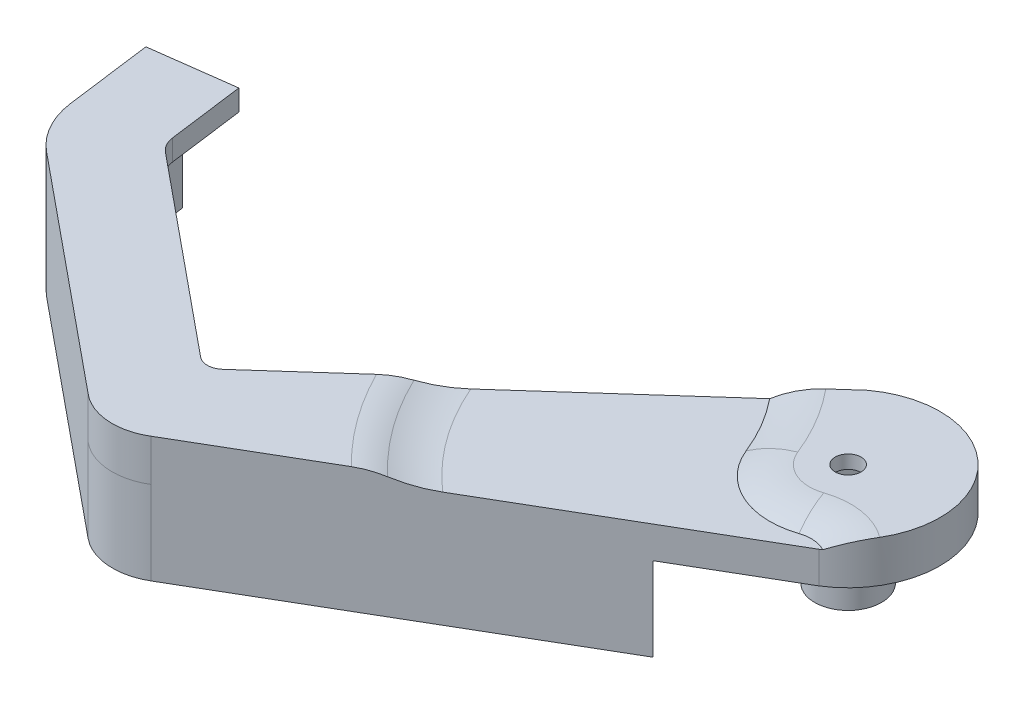
SolidWorks part; units mm, degrees
ref_plane "Front Plane" through (0, 0, 0) normal (0, 0, 1) x (1, 0, 0)
ref_plane "Top Plane" through (0, 0, 0) normal (0, 1, 0) x (1, 0, 0)
ref_plane "Right Plane" through (0, 0, 0) normal (1, 0, 0) x (0, 0, -1)
sketch "Sketch1" plane through (0, 0, 0) normal (0, 1, 0) x (1, 0, 0)
  circle A0 centre (0, 0) radius 10.3349
  dimension "D1" = 20.6698
extrude "Boss-Extrude1" add sketch "Sketch1" along normal blind 4
sketch "Sketch2" plane through (0, 0, 0) normal (0, -1, 0) x (1, 0, 0)
  circle A0 centre (0, 0) radius 4
other "Move Face1" flip direction yes face at (0, 0, 10.3349) offset 3 parameters "D1"=3
sketch "Sketch5" plane through (0, 3, 0) normal (0, -1, 0) x (1, 0, 0)
  line L0 (0, 0) -> (-48.7465, 34.9826) construction
  line L1 (-48.7465, 34.9826) -> (-78.7465, 10.3971) construction
  line L2 (0, 0) -> (-78.7465, 10.3971) construction
  line L3 (-78.7465, 10.3971) -> (-80.7177, -4.5326) construction
  line L5 (-75.4582, -2.5675) -> (-74.0969, 7.743)
  line L6 (-74.0969, 7.743) -> (-48.5447, 28.6834)
  line L12 (-6.5426, -8.8428) -> (-48.5447, 28.6834)
  line L13 (-52.8156, 38.1124) -> (-83.396, 13.0512)
  line L15 (-75.4582, -2.5675) -> (-85.2869, -1.2698)
  line L16 (-85.2869, -1.2698) -> (-83.396, 13.0512)
  line L17 (-44.6294, 38.7624) -> (5.2508, 9.6659)
  arc A1 (-52.8156, 38.1124) -> (-44.6294, 38.7624) centre (-48.2723, 32.7672) cw
  arc A3 (5.2508, 9.6659) -> (-6.5426, -8.8428) centre (0, 0) cw
  point P9 (-80.7177, -4.5326)
  point P15 (0, 0)
  dimension "D1" = 10.4
  dimension "D2" = 60
  dimension "D3" = 30
  dimension "D4" = 105
  dimension "D7" = 5
  dimension "D12" = 33.0367
extrude "Boss-Extrude3" add sketch "Sketch5" along normal blind 5
sketch "Sketch6" plane through (0, -2, 0) normal (0, -1, 0) x (1, 0, 0)
  circle A0 centre (0, 0) radius 6.3
  dimension "D1" = 12.6
extrude "Boss-Extrude4" add sketch "Sketch6" along normal blind 0.3
other "Move Face2" flip direction yes face at (0, 4, 10.3349) offset 1 parameters "D1"=1
sketch "Sketch8" plane through (0, -2, 0) normal (0, -1, 0) x (1, 0, 0)
  line L0 (-85.2869, -1.2698) -> (-81.4016, -1.7828)
  line L1 (-85.2869, -1.2698) -> (-75.4582, -2.5675) construction
  line L2 (-81.4016, -1.7828) -> (-79.6672, 11.3539)
  line L3 (-79.6672, 11.3539) -> (-48.9483, 36.5285)
  line L9 (-83.396, 13.0512) -> (-85.2869, -1.2698)
  line L10 (-12.814, 12.5754) -> (-48.9483, 36.5285)
  line L11 (-52.8156, 38.1124) -> (-83.396, 13.0512)
  line L12 (-44.6294, 38.7624) -> (-6.72, 16.6488)
  line L13 (-52.8156, 38.1124) -> (-83.396, 13.0512) construction
  arc A0 (-6.72, 16.6488) -> (-12.814, 12.5754) centre (0, 0) ccw
  arc A1 (-44.6294, 38.7624) -> (-52.8156, 38.1124) centre (-48.2574, 32.5794) ccw
  arc A2 (-44.6294, 38.7624) -> (-52.8156, 38.1124) centre (-48.2723, 32.7672) ccw construction
extrude "Boss-Extrude5" add sketch "Sketch8" along normal blind 10
sketch "Sketch9" plane through (0, -2, 0) normal (0, -1, 0) x (1, 0, 0)
  line L1 (-19.0217, 1.1217) -> (-75.4582, -2.5675)
  line L2 (-75.4582, -2.5675) -> (-81.4016, -1.7828)
  line L3 (-81.4016, -1.7828) -> (-79.6672, 11.3539)
  line L4 (-81.4016, -1.7828) -> (-79.6672, 11.3539) construction
  line L5 (-79.6672, 11.3539) -> (-48.9483, 36.5285)
  line L6 (-48.9483, 36.5285) -> (-13.7475, 13.1943)
  arc A0 (-13.7475, 13.1943) -> (-19.0217, 1.1217) centre (0, 0) ccw
  point P4 (0, 0)
  point P5 (0, 0)
  dimension "D1" = 1.12
extrude "Cut-Extrude3" cut sketch "Sketch9" against normal blind 2.5
ref_axis "Axis2" through (0, -2, 0) along (0, 1, 0)
ref_plane "Plane1" through (0, 0, 0) normal (-0.5525, 0, -0.8335) x (-0.8335, 0, 0.5525)
sketch "Sketch13" plane through (0, -2.3, 0) normal (0, -1, 0) x (1, 0, 0)
  circle A2 centre (0, 0) radius 4
  dimension "D1" = 8
extrude "Boss-Extrude6" add sketch "Sketch13" along normal blind 7
sketch "Sketch14" plane through (0, -9.3, 0) normal (0, -1, 0) x (1, 0, 0)
  circle A0 centre (0, 0) radius 1.55
  dimension "D1" = 3.1
extrude "Cut-Extrude6" cut sketch "Sketch14" against normal blind 14.3
ref_plane "Plane2" through (0, -1.1, 0) normal (0, -1, 0) x (-1, 0, 0)
sketch "Sketch15" plane through (0, -1.1, 0) normal (0, -1, 0) x (-1, 0, 0)
  line L1 (2.0704, -2.7773) -> (3.4404, 0.4043)
  line L2 (3.4404, 0.4043) -> (1.37, 3.1817)
  line L3 (1.37, 3.1817) -> (-2.0704, 2.7773)
  line L4 (-2.0704, 2.7773) -> (-3.4404, -0.4043)
  line L5 (-3.4404, -0.4043) -> (-1.37, -3.1817)
  line L6 (-1.37, -3.1817) -> (2.0704, -2.7773)
  circle A0 centre (0, 0) radius 3 construction
extrude "Cut-Extrude7" cut sketch "Sketch15" against normal blind 2.5
sketch "Sketch17" plane through (5.54, 0, 9.4972) normal (0.5039, 0, 0.8638) x (0.8638, 0, -0.5039)
  line L2 (-19.4143, -8.2622) -> (11.2348, -8.2622)
  line L3 (-19.4143, -8.2622) -> (-19.4143, 7.3647)
  line L4 (-19.4143, 7.3647) -> (11.2348, 7.3647)
  line L5 (11.2348, -8.2622) -> (11.2348, 7.3647)
revolve "Cut-Revolve1" cut sketch "Sketch17" angle 270 about L5
fillet "Fillet1" radius 10 1 edges at (-83.396, -4.5, 13.0512) type face fillet first side face at (-84.3415, -4.5, 5.8907) second side face at (-65.0478, -4, 28.088)
fillet "Fillet3" radius 10 1 edges at (-79.6672, -5.75, 11.3539)
fillet "Fillet4" radius 4.5 1 edges at (-48.9483, -5.75, 36.5285)
fillet "Fillet5" radius 2 1 edges at (-48.5447, 1.75, 28.6834)
fillet "Fillet6" radius 3 1 edges at (-74.0969, 1.75, 7.743)
sketch "Sketch19" plane through (0, 3, 0) normal (0, 1, 0) x (1, 0, 0)
  line L1 (5.8291, -9.3285) -> (-44.6294, -38.7624) construction
  line L8 (-36.1854, -17.6412) -> (-38.3255, -13.2245)
  line L9 (-47.2683, -27.5431) -> (-6.5426, 8.8428) construction
  line L10 (-38.3255, -13.2245) -> (-18.5658, 3.3299)
  line L11 (-18.5658, 3.3299) -> (-12.713, 3.3299)
  line L12 (6.1098, -9.1471) -> (9.9101, -16.99)
  line L13 (9.9101, -16.99) -> (-20.6659, -33.1303)
  line L14 (-20.6659, -33.1303) -> (-27.9109, -29.01)
  arc A0 (-36.1854, -17.6412) -> (-27.9109, -29.01) centre (0, 0) ccw
  arc A1 (3.0047, -8.8905) -> (-8.7152, -3.4805) centre (0, 0) cw
  arc A2 (-8.7152, -3.4805) -> (-12.713, 3.3299) centre (-33.1146, -13.2245) ccw
  arc A3 (3.0047, -8.8905) -> (6.1098, -9.1471) centre (4.2607, -12.6067) cw
  arc A4 (5.8291, -9.3285) -> (-6.5426, 8.8428) centre (0, 0) ccw construction
extrude "Cut-Extrude9" cut sketch "Sketch19" against normal blind 1.2 contours L14 A0 L8 L10 L11 A2 A1 A3 L12 L13
fillet "Fillet8" radius 15 1 edges at (-32.5484, 1.8, 23.6897)
fillet "Fillet9" radius 10 1 edges at (-32.5484, 3, 23.6897)
fillet "Fillet10" radius 10 2 edges at (4.5839, 3, 8.6973) (-10.4567, 3, -0.0758)
fillet "Fillet17" radius 100 1 edges at (-17.2331, 0.5, 8.1303)
fillet "Fillet19" radius 10 1 edges at (-17.2331, -2, 8.1303)
